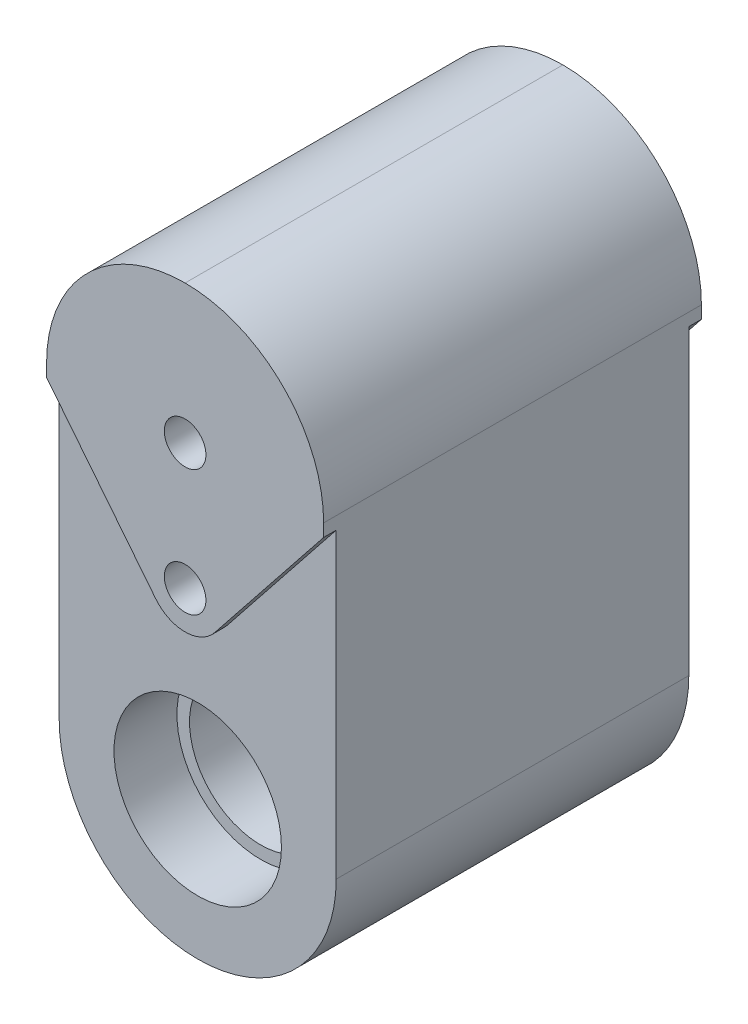
SolidWorks part; units mm, degrees
ref_plane "Спереди" through (0, 0, 0) normal (0, 0, 1) x (1, 0, 0)
ref_plane "Сверху" through (0, 0, 0) normal (0, 1, 0) x (1, 0, 0)
ref_plane "Справа" through (0, 0, 0) normal (1, 0, 0) x (0, 0, -1)
sketch "Эскиз1" plane through (0, 0, 0) normal (0, 0, 1) x (1, 0, 0)
  line L0 (0, 36) -> (0, -11) construction
  line L1 (-11, 36) -> (11, 36)
  line L2 (-11, 36) -> (-11, -11)
  line L3 (-11, -11) -> (11, -11)
  line L4 (11, 36) -> (11, -11)
  line L6 (-11, 0) -> (11, 0) construction
  dimension "D1" = 22
  dimension "D2" = 11
  dimension "D3" = 36
extrude "тело" add sketch "Эскиз1" along normal blind 14 and the other way blind 14
sketch "Эскиз2" plane through (0, 0, 14) normal (0, 0, 1) x (1, 0, 0)
  circle A0 centre (0, 0) radius 6.65
  dimension "D1" = 13.3
extrude "углубление для подшипника" cut sketch "Эскиз2" against normal blind 5
sketch "Эскиз4" plane through (0, 0, 9) normal (0, 0, 1) x (1, 0, 0)
  line L1 (0, 36) -> (0, -11) construction
  line L2 (-11, 0) -> (11, 0) construction
  circle A0 centre (0, 0) radius 5.65
  circle A1 centre (0, 0) radius 6.65 construction
  dimension "D1" = 1
extrude "сквозное отверстие" cut sketch "Эскиз4" against normal through all
mirror "Зеркальное отражение2" about plane through (0, 0, 0) normal (0, 0, 1) of "углубление для подшипника"
sketch "Эскиз5" plane through (0, 0, -14) normal (0, 0, -1) x (-1, 0, 0)
  line L0 (0, 36) -> (0, -11) construction
  line L1 (-11, 36) -> (11, 36) construction
  line L2 (11, -11) -> (-11, -11) construction
  circle A0 centre (0, 25) radius 1.65
  circle A1 centre (0, 15) radius 1.65
  circle A2 centre (0, 0) radius 6.65 construction
  dimension "D1" = 3.3
  dimension "D2" = 10
  dimension "D3" = 15
extrude "отверстия под болты" cut sketch "Эскиз5" against normal through all
sketch "Эскиз9" plane through (0, 0, 14) normal (0, 0, 1) x (1, 0, 0)
  line L0 (-11, 36) -> (-11, 24)
  line L1 (-11, 36) -> (-11, -11) construction
  line L2 (-11, 36) -> (11, 36)
  line L3 (-11, 24) -> (-2.347, 13.1314)
  line L4 (11, 36) -> (11, 24)
  line L5 (11, 24) -> (2.347, 13.1314)
  line L6 (11, -11) -> (11, 36) construction
  arc A0 (-2.347, 13.1314) -> (2.347, 13.1314) centre (0, 15) ccw
  circle A1 centre (0, 15) radius 1.65
  circle A2 centre (0, 25) radius 1.65
  circle A3 centre (0, 25) radius 1.65 construction
  circle A4 centre (0, 15) radius 1.65 construction
  point P4 (-2.7602, 13.8248)
  dimension "D1" = 6
  dimension "D2" = 12
extrude "выступы" add sketch "Эскиз9" along normal blind 1
mirror "Зеркальное отражение1" about plane through (0, 0, 0) normal (0, 0, 1) of "выступы"
fillet "Скругление1" radius 11 4 edges at (11, -11, 0) (-11, -11, 0) (-11, 36, 0) (11, 36, 0)
